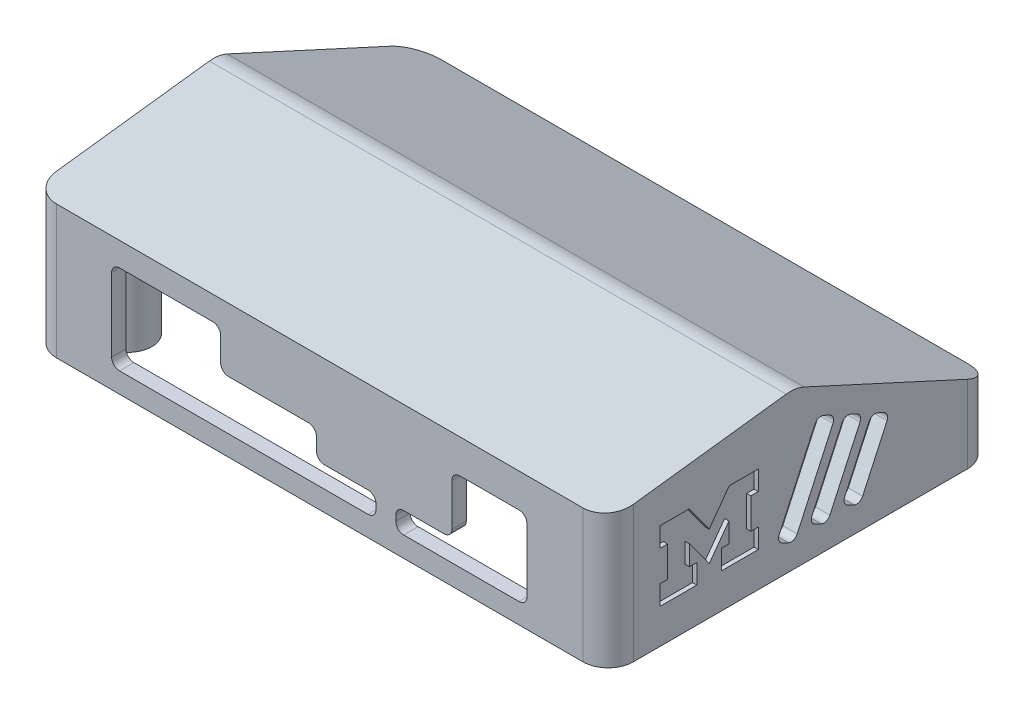
SolidWorks part; units mm, degrees
ref_plane "Front Plane" through (0, 0, 0) normal (0, 0, 1) x (1, 0, 0)
ref_plane "Top Plane" through (0, 0, 0) normal (0, 1, 0) x (1, 0, 0)
ref_plane "Right Plane" through (0, 0, 0) normal (1, 0, 0) x (0, 0, -1)
sketch "Sketch1" plane through (0, 0, 0) normal (0, 1, 0) x (1, 0, 0)
  line L0 (-37.7767, 21.1111) -> (-37.7767, -27.7389)
  line L1 (-34.6167, 23.6111) -> (43.3333, 23.6111)
  line L2 (-37.1167, 21.1111) -> (-37.1167, -27.7389)
  line L3 (-34.6167, -30.2389) -> (43.3333, -30.2389)
  line L4 (45.8333, 21.1111) -> (45.8333, -27.7389)
  line L5 (-34.6167, -30.8989) -> (43.3333, -30.8989)
  line L6 (46.4933, 21.1111) -> (46.4933, -27.7389)
  line L7 (-34.6167, 24.2711) -> (43.3333, 24.2711)
  arc A0 (-37.1167, -27.7389) -> (-34.6167, -30.2389) centre (-34.6167, -27.7389) ccw
  arc A1 (43.3333, -30.2389) -> (45.8333, -27.7389) centre (43.3333, -27.7389) ccw
  arc A2 (43.3333, 23.6111) -> (45.8333, 21.1111) centre (43.3333, 21.1111) cw
  arc A3 (-34.6167, 23.6111) -> (-37.1167, 21.1111) centre (-34.6167, 21.1111) ccw
  arc A4 (-37.7767, -27.7389) -> (-34.6167, -30.8989) centre (-34.6167, -27.7389) ccw
  arc A5 (43.3333, -30.8989) -> (46.4933, -27.7389) centre (43.3333, -27.7389) ccw
  arc A6 (43.3333, 24.2711) -> (46.4933, 21.1111) centre (43.3333, 21.1111) cw
  arc A7 (-34.6167, 24.2711) -> (-37.7767, 21.1111) centre (-34.6167, 21.1111) ccw
  point P8 (45.8333, -30.2389)
  point P11 (45.8333, 23.6111)
  point P14 (-37.1167, 23.6111)
  dimension "D3" = 2.5
  dimension "D1" = 82.95
  dimension "D2" = 53.85
  dimension "D4" = 0.66
extrude "Boss-Extrude1" add sketch "Sketch1" along normal blind 1.8
sketch "Sketch3" plane through (0, 1.8, 0) normal (0, 1, 0) x (1, 0, 0)
  line L8 (43.3333, 21.5611) -> (-34.6167, 21.5611)
  line L9 (-35.0667, 21.1111) -> (-35.0667, -27.7389)
  line L10 (-37.1167, 21.1111) -> (-37.1167, -27.7389)
  line L11 (-34.6167, -30.2389) -> (43.3333, -30.2389)
  line L33 (45.8333, -27.7389) -> (45.8333, 21.1111)
  line L34 (43.3333, 23.6111) -> (-34.6167, 23.6111)
  line L35 (-39.2917, 21.1111) -> (-39.2917, 25.7861)
  line L36 (-39.2917, 25.7861) -> (-34.6167, 25.7861)
  line L37 (43.3333, 25.7861) -> (-34.6167, 25.7861)
  line L38 (-39.2917, 21.1111) -> (-39.2917, -27.7389)
  line L39 (-34.6167, -32.4139) -> (43.3333, -32.4139)
  line L40 (48.0083, -27.7389) -> (48.0083, 21.1111)
  line L41 (43.3333, 25.7861) -> (-34.6167, 25.7861)
  line L42 (-39.2917, 21.1111) -> (-39.2917, -27.7389)
  line L43 (-34.6167, -32.4139) -> (43.3333, -32.4139)
  line L44 (48.0083, -27.7389) -> (48.0083, 21.1111)
  line L45 (-34.6167, 25.7861) -> (-34.5188, 25.7484)
  line L46 (48.0083, 21.1111) -> (48.0083, 25.7861)
  line L47 (48.0083, 25.7861) -> (43.3333, 25.7861)
  line L48 (43.3333, 25.7861) -> (43.4732, 25.7999)
  line L49 (48.0083, -27.7389) -> (48.0083, -32.4139)
  line L50 (48.0083, -32.4139) -> (43.3333, -32.4139)
  line L51 (-39.2917, -27.7389) -> (-39.2917, -32.4139)
  line L52 (-39.2917, -32.4139) -> (-34.6167, -32.4139)
  arc A6 (43.7833, 21.1111) -> (43.3333, 21.5611) centre (43.3333, 21.1111) ccw
  arc A7 (-34.6167, 21.5611) -> (-35.0667, 21.1111) centre (-34.6167, 21.1111) ccw
  arc A8 (43.7833, 21.1111) -> (43.3333, 21.5611) centre (43.3333, 21.1111) ccw
  arc A9 (-37.1167, -27.7389) -> (-34.6167, -30.2389) centre (-34.6167, -27.7389) ccw
  arc A21 (43.3333, -30.2389) -> (45.8333, -27.7389) centre (43.3333, -27.7389) ccw
  arc A22 (45.8333, 21.1111) -> (43.3333, 23.6111) centre (43.3333, 21.1111) ccw
  arc A23 (-34.6167, 23.6111) -> (-37.1167, 21.1111) centre (-34.6167, 21.1111) ccw
  arc A25 (43.3333, -32.4139) -> (48.0083, -27.7389) centre (43.3333, -27.7389) ccw
  arc A26 (48.0083, 21.1111) -> (43.3333, 25.7861) centre (43.3333, 21.1111) ccw
  arc A27 (-34.6167, 25.7861) -> (-39.2917, 21.1111) centre (-34.6167, 21.1111) ccw
  arc A28 (-39.2917, -27.7389) -> (-34.6167, -32.4139) centre (-34.6167, -27.7389) ccw
  arc A29 (43.3333, -32.4139) -> (48.0083, -27.7389) centre (43.3333, -27.7389) ccw
  arc A30 (48.0083, 21.1111) -> (43.3333, 25.7861) centre (43.3333, 21.1111) ccw
  arc A31 (-34.6167, 25.7861) -> (-39.2917, 21.1111) centre (-34.6167, 21.1111) ccw
  arc A32 (-39.2917, -27.7389) -> (-34.6167, -32.4139) centre (-34.6167, -27.7389) ccw
  arc M13 (-34.6167, 24.2711) -> (-37.7767, 21.1111) centre (-34.6167, 21.1111) ccw
  line M14 (-37.7767, 21.1111) -> (-37.7767, -27.7389)
  arc M15 (-37.7767, -27.7389) -> (-34.6167, -30.8989) centre (-34.6167, -27.7389) ccw
  line M16 (-34.6167, -30.8989) -> (43.3333, -30.8989)
  arc M17 (43.3333, -30.8989) -> (46.4933, -27.7389) centre (43.3333, -27.7389) ccw
  line M18 (46.4933, -27.7389) -> (46.4933, 21.1111)
  arc M19 (46.4933, 21.1111) -> (43.3333, 24.2711) centre (43.3333, 21.1111) ccw
  line M20 (43.3333, 24.2711) -> (-34.6167, 24.2711)
  line M21 (43.3333, -30.2389) -> (-34.6167, -30.2389)
  arc M22 (-34.6167, -30.2389) -> (-37.1167, -27.7389) centre (-34.6167, -27.7389) cw
  line M23 (-37.1167, -27.7389) -> (-37.1167, 21.1111)
  arc M24 (-37.1167, 21.1111) -> (-34.6167, 23.6111) centre (-34.6167, 21.1111) cw
  line M25 (-34.6167, 23.6111) -> (43.3333, 23.6111)
  arc M26 (43.3333, 23.6111) -> (45.8333, 21.1111) centre (43.3333, 21.1111) cw
  line M27 (45.8333, 21.1111) -> (45.8333, -27.7389)
  arc M28 (45.8333, -27.7389) -> (43.3333, -30.2389) centre (43.3333, -27.7389) cw
  dimension "D1" = 2.05
  dimension "D2" = 2.175
  dimension "D3" = 2.175
extrude "Boss-Extrude3" add sketch "Sketch3" along normal blind 10 contours L42 A32 L43 A29 L44 A30 L41 A31 M13 M20 M19 M18 M17 M16 M15 M14 | A32 L51 L52 | M20 M13 M14 M15 M16 M17 M18 M19 M28 M21 M22 M23 M24 M25 M26 M27 | A31 L36 L35 | A30 L46 L47 | A29 L50 L49 region at (-37.1805, 1.8, -23.6749) region at (-38.2474, 1.8, -24.7419) region at (-38.2474, 1.8, 31.3696) region at (46.9641, 1.8, -24.7419) region at (46.9641, 1.8, 31.3696) region at (4.3583, 1.8, -24.1704)
sketch "Sketch4" plane through (0, 0, -25.7861) normal (0, 0, -1) x (-1, 0, 0)
  line L0 (-4.3583, 1.8) -> (-4.3583, 25.0723)
  line L1 (-48.0083, 1.8) -> (39.2917, 1.8) construction
  line L2 (7.9607, 1.8) -> (7.9607, 25.0723)
  line L3 (20.6617, 1.8) -> (20.6617, 22.638)
  line L4 (7.9607, 5.44) -> (20.6617, 5.44)
  line L5 (4.5182, 1.8) -> (4.5182, -0.6587)
  line L6 (11.4031, 1.8) -> (11.4031, -0.6587)
  line L7 (11.4031, -0.6587) -> (4.5182, -0.6587)
  line L8 (17.2192, 1.8) -> (17.2192, -1.5181)
  line L9 (24.1041, -1.5181) -> (17.2192, -1.5181)
  line L10 (24.1041, 1.8) -> (24.1041, -1.5181)
  line L11 (-48.0083, 1.8) -> (39.2917, 1.8) construction
  circle A0 centre (7.9607, 5.44) radius 5.01
  circle A1 centre (20.6617, 5.44) radius 5.01
  line M1 (-48.0083, 1.8) -> (39.2917, 1.8)
  dimension "D4" = 10.02
  dimension "D5" = 10.02
  dimension "D2" = 25.02
  dimension "D3" = 3.64
  dimension "D1" = 12.319
extrude "Cut-Extrude1" cut sketch "Sketch4" against normal blind 5 contours L2 A0 M1 | A0 L4 L2 M1 | L4 A0 L2 | A0 L5 L7 L6 | A0 M1 | A1 L8 L9 L10 | A1 region at (-5.762, 5.8158, -25.7861) region at (-7.9607, 1.245, -25.7861) region at (-10.246, 3.7208, -25.7861) region at (-10.087, 7.5663, -25.7861) region at (-7.9607, 0.1521, -25.7861) region at (-20.6617, -0.2965, -25.7861)
sketch "Sketch5" plane through (0, 0, -25.7861) normal (0, 0, -1) x (-1, 0, 0)
  line L0 (-4.3583, 11.8) -> (-4.3583, -7.2365)
  line L1 (-48.0083, 11.8) -> (39.2917, 11.8) construction
  line L2 (-17.3383, 11.8) -> (-17.3383, -7.2365)
  line L3 (-48.0083, 1.8) -> (4.5182, 1.8) construction
  line L5 (-17.3383, 1.8) -> (-17.3383, 8.55)
  line L6 (-17.3383, 8.55) -> (-10.9347, 8.55)
  line L8 (-4.6583, 11.8) -> (-4.6583, -7.2365)
  line L9 (-4.6583, 8.55) -> (-7.6243, 8.55)
  circle A0 centre (-17.3383, 8.55) radius 1.69
  circle A1 centre (-17.3383, 8.55) radius 2.19
  circle A2 centre (-4.6583, 8.55) radius 1.69
  circle A3 centre (-4.6583, 8.55) radius 2.19
  dimension "D3" = 3.38
  dimension "D6" = 3.38
  dimension "D2" = 6.75
  dimension "D1" = 12.98
  dimension "D4" = 0.5
  dimension "D5" = 0.3
  dimension "D7" = 0.5
extrude "Cut-Extrude2" cut sketch "Sketch5" against normal blind 5 contours A3 | A1
sketch "Sketch6" plane through (0, 11.8, 0) normal (0, 1, 0) x (1, 0, 0)
  line L0 (-37.1167, -3.3139) -> (-39.2917, -3.3139)
  line L2 (-37.1167, -27.7389) -> (-37.1167, 21.1111) construction
  line L3 (-37.1167, -3.3139) -> (45.8333, -3.3139)
  line L4 (45.8333, 21.1111) -> (45.8333, -27.7389) construction
  line L5 (45.8333, -3.3139) -> (48.0083, -3.3139)
  line L19 (48.0083, -28.6139) -> (48.0083, -32.4139)
  line L20 (48.0083, -32.4139) -> (44.2083, -32.4139)
  line L21 (-39.2917, -28.6139) -> (-39.2917, -32.4139)
  line L22 (48.0083, -28.6139) -> (48.0083, 25.7861)
  line L23 (-35.4917, -32.4139) -> (44.2083, -32.4139)
  line L24 (-39.2917, 25.7861) -> (-39.2917, -28.6139)
  line L31 (-39.2917, -32.4139) -> (-35.4917, -32.4139)
  line L37 (45.8333, 21.1111) -> (45.8333, -27.7389)
  line L38 (43.3333, -30.2389) -> (-34.6167, -30.2389)
  line L39 (-37.1167, -27.7389) -> (-37.1167, 21.1111)
  arc A20 (43.3333, -30.2389) -> (45.8333, -27.7389) centre (43.3333, -27.7389) ccw
  arc A21 (-37.1167, -27.7389) -> (-34.6167, -30.2389) centre (-34.6167, -27.7389) ccw
  line M11 (-39.2917, 25.7861) -> (-39.2917, -32.4139)
  line M13 (-39.2917, -32.4139) -> (48.0083, -32.4139)
  line M15 (48.0083, -32.4139) -> (48.0083, 25.7861)
  arc M19 (45.8333, -27.7389) -> (43.3333, -30.2389) centre (43.3333, -27.7389) cw
  line M20 (43.3333, -30.2389) -> (-34.6167, -30.2389)
  arc M21 (-34.6167, -30.2389) -> (-37.1167, -27.7389) centre (-34.6167, -27.7389) cw
  line M22 (-37.1167, -27.7389) -> (-37.1167, 21.1111)
  line M26 (45.8333, 21.1111) -> (45.8333, -27.7389)
  dimension "D3" = 29.1
extrude "Boss-Extrude4" add sketch "Sketch6" along normal blind 8 contours M26 M19 M20 M21 M22 M11 M13 M15 region at (-38.0369, 11.8, 15.5264)
sketch "Sketch7" plane through (0, 19.8, 0) normal (0, 1, 0) x (1, 0, 0)
  line L0 (-39.2917, -30.2389) -> (48.0083, -30.2389)
  line L1 (48.0083, -31.3688) -> (48.0083, -32.4139)
  line L2 (48.0083, -32.4139) -> (44.2083, -32.4139)
  line L3 (-39.2917, -31.3688) -> (-39.2917, -32.4139)
  line L4 (-39.2917, -32.4139) -> (-35.4917, -32.4139)
  line L8 (43.3333, -30.2389) -> (-34.6167, -30.2389) construction
  line L9 (-39.2917, -3.3139) -> (-39.2917, -32.4139) construction
  line L10 (48.0083, -32.4139) -> (48.0083, -3.3139) construction
  line L19 (-35.4917, -32.4139) -> (44.2083, -32.4139)
  line L20 (-39.2917, -30.2389) -> (-39.2917, -31.3688)
  line L21 (48.0083, -31.3688) -> (48.0083, -30.2389)
  dimension "D1" = 2.175
  dimension "D2" = 2.175
extrude "Boss-Extrude5" add sketch "Sketch7" along normal blind 2.175
sketch "Sketch15" plane through (0, 0, 32.4139) normal (0, 0, 1) x (1, 0, 0)
  line L0 (4.3583, 4.8675) -> (4.3583, 8.0675)
  line L1 (-39.2917, 1.8) -> (48.0083, 1.8) construction
  line L2 (-39.2917, 21.975) -> (48.0083, 21.975) construction
  line L3 (-27.1327, 4.8675) -> (12.8673, 4.8675)
  line L4 (-27.1327, 4.8675) -> (12.8673, 4.8675)
  line L6 (-18.8827, 4.8675) -> (-18.8827, 18.3675)
  line L7 (-10.6327, 4.8675) -> (-10.6327, 18.3675)
  line L8 (-27.1327, 4.8675) -> (-27.1327, 18.3675)
  line L9 (-27.1327, 18.3675) -> (-10.6327, 18.3675)
  line L10 (4.3583, 18.3675) -> (48.0083, 18.3675)
  line L11 (-39.2917, 18.3675) -> (48.0083, 18.3675) construction
  line L12 (-27.1327, 1.8) -> (-27.1327, 21.975) construction
  line L13 (-10.6327, 1.8) -> (-10.6327, 21.975) construction
  line L14 (3.8673, 4.8675) -> (3.8673, 12.3675)
  line L15 (-10.6327, 12.3675) -> (3.8673, 12.3675)
  line L16 (12.8673, 4.8675) -> (12.8673, 8.0675)
  line L17 (3.8673, 4.8675) -> (3.8673, 18.3675) construction
  line L18 (3.8673, 8.0675) -> (12.8673, 8.0675)
  line L19 (15.8673, 4.8675) -> (15.8673, 8.0675)
  line L20 (12.8673, 4.8675) -> (12.8673, 12.3675) construction
  line L22 (15.8673, 8.0675) -> (24.3673, 8.0675)
  line L23 (30.4695, 4.8675) -> (30.4695, 16.8675)
  line L24 (35.7195, 4.8675) -> (35.7195, 16.8675)
  line L26 (25.2195, 16.8675) -> (35.7195, 16.8675)
  line L27 (25.2195, 18.3675) -> (25.2195, 21.975)
  line L28 (35.7195, 18.3675) -> (35.7195, 21.975)
  line L30 (4.3583, 18.3675) -> (4.3583, 21.975)
  line L31 (35.7195, 1.8) -> (35.7195, 21.975) construction
  line L32 (-18.8827, 1.8) -> (-18.8827, 21.975) construction
  line L33 (-39.2917, 4.8675) -> (48.0083, 4.8675) construction
  line L34 (25.2195, 4.8675) -> (35.7195, 4.8675)
  line L35 (4.3583, 1.8) -> (4.3583, 21.975) construction
  line L36 (30.4695, 1.8) -> (30.4695, 21.975) construction
  line L37 (15.8673, 4.8675) -> (24.3673, 4.8675)
  line L38 (30.4695, 18.3675) -> (30.4695, 21.975)
  line L39 (-27.1327, 4.8675) -> (-27.1327, 18.3675)
  line L40 (-10.6327, 18.3675) -> (-10.6327, 12.3675)
  line L41 (3.8673, 12.3675) -> (3.8673, 8.0675)
  line L42 (15.8673, 4.8675) -> (24.3673, 4.8675)
  line L44 (35.7195, 16.8675) -> (35.7195, 4.8675)
  line L45 (25.2195, 4.8675) -> (35.7195, 4.8675)
  line L46 (25.2195, 16.8675) -> (24.3673, 16.8675)
  line L47 (24.3673, 16.8675) -> (24.3673, 8.0675)
  line L48 (24.3673, 4.8675) -> (25.2195, 4.8675)
  point P41 (25.2195, 1.8)
  dimension "D1" = 3.0675
  dimension "D7" = 7.5
  dimension "D9" = 3.2
  dimension "D15" = 12
  dimension "D2" = 23.241
  dimension "D3" = 8.25
  dimension "D4" = 8.25
  dimension "D5" = 13.5
  dimension "D6" = 14.5
  dimension "D8" = 9
  dimension "D10" = 3
  dimension "D12" = 26.1112
  dimension "D13" = 5.25
extrude "Cut-Extrude3" cut sketch "Sketch15" against normal blind 2.175 contours L9 L8 L3 L6 | L9 L6 L4 L7 | L15 L7 L3 L14 | L18 L0 L3 L16 | L18 L14 L4 L0 | L19 L37 L22 | L34 L23 L26 | L23 L34 L24 L26 region at (4.1128, 6.4675, 32.4139) region at (8.6128, 6.4675, 32.4139) region at (-3.3827, 8.6175, 32.4139) region at (-14.7577, 11.6175, 32.4139) region at (-23.0077, 11.6175, 32.4139) region at (25.441, 9.6758, 32.4139) region at (33.0945, 10.8675, 32.4139)
sketch "Sketch24" plane through (-39.2917, 0, 0) normal (-1, 0, 0) x (0, 0, 1)
  line L0 (32.146, 19.8166) -> (4.3973, 23.2604)
  line L1 (4.3973, 23.2604) -> (-20.572, 11.8)
  line L2 (32.146, 19.8166) -> (32.4139, 19.8166)
  line L3 (32.4139, 21.975) -> (32.4139, 1.8) construction
  line L4 (32.4139, 19.8166) -> (32.4139, 21.975)
  line L5 (-25.7861, 11.8) -> (-20.572, 11.8)
  line L10 (4.3973, 23.2604) -> (-24.8788, 9.8233) construction
  line L23 (32.4139, 21.975) -> (4.0518, 25.495)
  line L24 (4.0518, 25.495) -> (-25.7861, 11.8)
  dimension "D1" = 2.175
extrude "Boss-Extrude11" add sketch "Sketch24" against normal up to surface (87.3 mm away) up to face at (48.0083, 14.4797, 13.5467)
sketch "Sketch28" plane through (-39.2917, 0, 0) normal (-1, 0, 0) x (0, 0, 1)
  line L0 (-20.572, 11.8) -> (4.3973, 23.2604)
  line L1 (4.3973, 23.2604) -> (30.2389, 20.0533)
  line L2 (30.2389, 20.0533) -> (30.2389, 19.8)
  line L3 (30.2389, 19.8) -> (3.3139, 19.8)
  line L4 (3.3139, 19.8) -> (3.3139, 11.8)
  line L5 (3.3139, 11.8) -> (-20.572, 11.8)
extrude "Boss-Extrude12" add sketch "Sketch28" against normal blind 2.175
sketch "Sketch29" plane through (48.0083, 0, 0) normal (1, 0, 0) x (0, 0, -1)
  line L0 (-30.2389, 20.0533) -> (-30.2389, 19.8)
  line L1 (-30.2389, 19.8) -> (-3.3139, 19.8)
  line L2 (-3.3139, 19.8) -> (-3.3139, 11.8)
  line L3 (-3.3139, 11.8) -> (20.572, 11.8)
  line L4 (20.572, 11.8) -> (-4.3973, 23.2604)
  line L5 (-4.3973, 23.2604) -> (-30.2389, 20.0533)
extrude "Boss-Extrude13" add sketch "Sketch29" against normal blind 2.175
sketch "Sketch32" plane through (48.0083, 0, 0) normal (1, 0, 0) x (0, 0, -1)
  line L0 (0.7555, 23.2886) -> (-6.9465, 6.5079)
  line L1 (25.7861, 11.8) -> (-4.0518, 25.495) construction
  line L2 (-6.9465, 6.5079) -> (-4.22, 5.2564)
  line L3 (-4.22, 5.2564) -> (2.0259, 18.8647)
  line L4 (2.0259, 18.8647) -> (-0.7006, 20.1161)
  line L5 (-2.8567, 4.6307) -> (-2.5695, 5.2564)
  line L7 (-1.9952, 6.5079) -> (3.3892, 18.239)
  line L8 (0.7314, 5.2564) -> (6.1157, 16.9876)
  line L9 (0.7314, 5.2564) -> (-1.9952, 6.5079)
  line L10 (-0.1302, 3.3793) -> (6.1157, 16.9876) construction
  line L12 (-2.8567, 4.6307) -> (3.3892, 18.239) construction
  line L14 (5.6827, 5.2564) -> (10.2055, 15.1104)
  line L16 (6.1157, 16.9876) -> (3.3892, 18.239)
  line L17 (7.479, 16.3618) -> (10.2055, 15.1104)
  line L18 (5.6827, 5.2564) -> (2.9562, 6.5079)
  line L19 (2.9562, 6.5079) -> (7.479, 16.3618)
  point P11 (2.0946, 4.6307)
  point P16 (3.4579, 4.005)
  point P17 (8.8422, 15.7361)
  point P18 (4.8211, 3.3793)
  dimension "D1" = 3
  dimension "D2" = 1.5
  dimension "D3" = 3
extrude "Cut-Extrude6" cut sketch "Sketch32" against normal through all contours L3 L4 L0 L2 | L8 L16 L7 L9 | L19 L18 L14 L17 region at (48.0083, 12.6863, 2.4603) region at (48.0083, 11.7477, -2.0603) region at (48.0083, 10.8091, -6.5808)
fillet "Fillet7" radius 1 24 edges at (46.9208, 5.2564, 4.22) (46.9208, 5.2564, -0.7314) (46.9208, 5.2564, -5.6827) (46.9208, 18.8647, -2.0259) (46.9208, 16.9876, -6.1157) (46.9208, 15.1104, -10.2055) (46.9208, 6.5079, 6.9465) (46.9208, 6.5079, 1.9952) (46.9208, 6.5079, -2.9562) (46.9208, 16.3618, -7.479) (46.9208, 20.1161, 0.7006) (46.9208, 18.239, -3.3892) (-38.2042, 16.9876, -6.1157) (-38.2042, 18.8647, -2.0259) (-38.2042, 15.1104, -10.2055) (-38.2042, 5.2564, -5.6827) (-38.2042, 5.2564, -0.7314) (-38.2042, 6.5079, -2.9562) (-38.2042, 6.5079, 1.9952) (-38.2042, 6.5079, 6.9465) (-38.2042, 16.3618, -7.479) (-38.2042, 18.239, -3.3892) (-38.2042, 20.1161, 0.7006) (-38.2042, 5.2564, 4.22)
fillet "Fillet1" radius 3.8 2 edges at (-39.2917, 11.8875, 32.4139) (48.0083, 11.8875, 32.4139)
fillet "Fillet2" radius 3.8 2 edges at (-39.2917, 6.8, -25.7861) (48.0083, 6.8, -25.7861)
fillet "Fillet4" radius 1.2 14 edges at (15.8673, 4.8675, 31.3264) (35.7195, 4.8675, 31.3264) (12.8673, 4.8675, 31.3264) (15.8673, 8.0675, 31.3264) (35.7195, 16.8675, 31.3264) (3.8673, 8.0675, 31.3264) (12.8673, 8.0675, 31.3264) (3.8673, 12.3675, 31.3264) (-10.6327, 18.3675, 31.3264) (-10.6327, 12.3675, 31.3264) (-27.1327, 18.3675, 31.3264) (-27.1327, 4.8675, 31.3264) (24.3673, 16.8675, 31.3264) (24.3673, 8.0675, 31.3264)
fillet "Fillet6" [suppressed] radius 1.5
sketch "Sketch20" plane through (0, 0, 0) normal (0, -1, 0) x (1, 0, 0)
  line L2 (-31.9917, -18.4361) -> (-37.1167, -18.4361) construction
  line L3 (-37.1167, -21.1111) -> (-37.1167, 27.7389) construction
  line L4 (40.7083, -18.4361) -> (45.8333, -18.4361) construction
  line L5 (45.8333, 27.7389) -> (45.8333, -21.1111) construction
  line L6 (-31.9917, 25.0639) -> (-31.9917, 30.2389) construction
  line L7 (-34.6167, 30.2389) -> (43.3333, 30.2389) construction
  line L8 (-31.9917, -18.4361) -> (-31.9917, -23.6111) construction
  line L9 (-24.1041, -23.6111) -> (-34.6167, -23.6111) construction
  circle A0 centre (-31.9917, -18.4361) radius 3.6
  circle A1 centre (-31.9917, -18.4361) radius 2.125
  circle A2 centre (40.7083, -18.4361) radius 2.125
  circle A3 centre (40.7083, -18.4361) radius 3.6
  circle A4 centre (40.7083, 25.0639) radius 2.125
  circle A5 centre (40.7083, 25.0639) radius 3.6
  circle A6 centre (-31.9917, 25.0639) radius 2.125
  circle A7 centre (-31.9917, 25.0639) radius 3.6
  dimension "D1" = 7.2
  dimension "D2" = 4.25
  dimension "D7" = 4.25
  dimension "D8" = 4.25
  dimension "D9" = 4.25
  dimension "D5" = 72.7
  dimension "D6" = 43.5
  dimension "D3" = 2
  dimension "D4" = 2
extrude "Boss-Extrude9" add sketch "Sketch20" against normal up to surface (18.0123 mm away) from offset 3.13 contours A5 A4 | A7 A6 region at (37.2102, 0, 25.0639) region at (-35.4898, 0, 25.0639) up to face at (4.3583, 21.6568, 17.3181) offset against normal yes
sketch "Sketch22" plane through (-39.2917, 0, 0) normal (-1, 0, 0) x (0, 0, 1)
  line L0 (28.6139, 1.8) -> (37.2656, 1.8)
  line L1 (37.2656, 1.8) -> (37.2656, 0)
  line L2 (37.2656, 0) -> (-27.0337, 0)
  line L3 (-27.0337, 0) -> (-27.0337, 1.8)
  line L4 (-27.0337, 1.8) -> (28.6139, 1.8)
extrude "Cut-Extrude4" cut sketch "Sketch22" against normal through all
sketch "Sketch23" plane through (-39.2917, 0, 0) normal (-1, 0, 0) x (0, 0, 1)
  line L0 (3.3139, 1.8) -> (3.3139, 3.3)
  line L1 (-21.9861, 1.8) -> (28.6139, 1.8) construction
  line L2 (3.3139, 3.3) -> (-5.2861, 3.3)
  line L3 (-5.2861, 3.3) -> (-5.2861, 1.8)
  line L4 (-5.2861, 1.8) -> (7.2139, 1.8)
  line L5 (7.2139, 1.8) -> (7.2139, 3.3)
  line L6 (7.2139, 3.3) -> (3.3139, 3.3)
  line M4 (-21.9861, 1.8) -> (28.6139, 1.8)
  dimension "D1" = 1.5
  dimension "D2" = 8.6
  dimension "D3" = 12.5
extrude "Cut-Extrude5" cut sketch "Sketch23" against normal blind 2.175 contours L2 L3 L0 M4 | L5 L6 L0 M4 region at (-39.2917, 2.55, -0.9861) region at (-39.2917, 2.55, 5.2639)
extrude "Boss-Extrude14" add sketch "Sketch20<4>" against normal up to next from offset 3.13 contours A3 A2 | A0 A1 region at (-35.4898, 0, -18.4361) region at (37.2102, 0, -18.4361) offset against normal yes
sketch "Sketch20<4>" plane through (0, 0, 0) normal (0, -1, 0) x (1, 0, 0) same geometry as "Sketch20"
fillet "Fillet8" radius 5 1 edges at (4.3583, 25.495, 4.0518)
sketch "Sketch33" plane through (48.0083, 0, 0) normal (1, 0, 0) x (0, 0, -1)
  line L0 (-24.5468, 17.6178) -> (-24.5468, 14.6578)
  line L1 (-24.5468, 14.6578) -> (-23.4268, 14.6578)
  line L2 (-23.4268, 14.6578) -> (-23.4268, 10.0178)
  line L3 (-23.4268, 10.0178) -> (-24.5468, 10.0178)
  line L4 (-24.5468, 10.0178) -> (-24.5468, 7.0578)
  line L5 (-24.5468, 7.0578) -> (-18.9948, 7.0578)
  line L6 (-18.9948, 7.0578) -> (-18.9948, 10.0178)
  line L7 (-18.9948, 10.0178) -> (-20.1148, 10.0178)
  line L8 (-20.1148, 10.0178) -> (-20.1148, 13.0258)
  line L9 (-20.1148, 13.0258) -> (-17.1228, 8.9315)
  line L11 (-17.1228, 13.4578) -> (-14.0828, 17.6178)
  line L12 (-14.1308, 13.0258) -> (-17.1228, 8.9315)
  line L13 (-14.0828, 17.6178) -> (-9.6988, 17.6178)
  line L14 (-14.1308, 10.0178) -> (-14.1308, 13.0258)
  line L15 (-15.2508, 10.0178) -> (-14.1308, 10.0178)
  line L16 (-15.2508, 7.0578) -> (-15.2508, 10.0178)
  line L17 (-9.6988, 7.0578) -> (-15.2508, 7.0578)
  line L18 (-9.6988, 10.0178) -> (-9.6988, 7.0578)
  line L19 (-10.8188, 10.0178) -> (-9.6988, 10.0178)
  line L20 (-10.8188, 14.6578) -> (-10.8188, 10.0178)
  line L21 (-9.6988, 14.6578) -> (-10.8188, 14.6578)
  line L22 (-17.1228, 13.4578) -> (-20.1628, 17.6178)
  line L23 (-20.1628, 17.6178) -> (-24.5468, 17.6178)
  line L24 (-9.6988, 17.6178) -> (-9.6988, 14.6578)
extrude "Cut-Extrude7" cut sketch "Sketch33" against normal blind 0.65
sketch "Sketch34" plane through (0, 3.13, 0) normal (0, -1, 0) x (1, 0, 0)
  line L0 (-34.0584, 27.1602) -> (-35.4917, 28.6139)
  line L1 (-35.4917, 28.6139) -> (-37.0054, 30.1493)
  line L2 (-33.3463, 27.8622) -> (-34.7796, 29.316)
  line L3 (-34.7796, 29.316) -> (-36.2933, 30.8514)
  line L4 (-34.7705, 26.4581) -> (-36.2038, 27.9118)
  line L5 (-36.2038, 27.9118) -> (-37.7175, 29.4472)
  line L6 (-37.7175, 29.4472) -> (-36.2933, 30.8514)
  line L7 (-33.3463, 27.8622) -> (-34.7705, 26.4581)
  line L8 (4.3583, 4.3973) -> (4.3583, 42.8593)
  line L9 (-36.2038, 27.9118) -> (-41.7788, 33.5665) construction
  line L10 (-35.4917, 28.6139) -> (-41.0667, 34.2685) construction
  line L11 (-34.7796, 29.316) -> (-40.3546, 34.9706) construction
  line L12 (-31.2796, 25.766) -> (-34.7796, 29.316) construction
  line L13 (-31.9917, 25.0639) -> (-35.4917, 28.6139) construction
  line L14 (-32.7038, 24.3618) -> (-36.2038, 27.9118) construction
  line L15 (45.8333, 4.3973) -> (-37.1167, 4.3973) construction
  line L16 (42.063, 27.8622) -> (43.4872, 26.4581)
  line L17 (46.4342, 29.4472) -> (45.01, 30.8514)
  line L18 (44.9204, 27.9118) -> (46.4342, 29.4472)
  line L19 (43.4872, 26.4581) -> (44.9204, 27.9118)
  line L20 (43.4962, 29.316) -> (45.01, 30.8514)
  line L21 (42.063, 27.8622) -> (43.4962, 29.316)
  line L22 (44.2083, 28.6139) -> (45.7221, 30.1493)
  line L23 (42.7751, 27.1602) -> (44.2083, 28.6139)
  line L24 (4.3583, 4.3973) -> (27.2788, 4.3973)
  dimension "D1" = 1
  dimension "D2" = 1
extrude "Boss-Extrude16" add sketch "Sketch34" against normal up to surface (17.0215 mm away) contours L23 L19 L18 L17 L22 | L23 L22 L17 L20 L21 | L16 L23 L21 | L23 L16 L19 | L4 L5 L6 L3 L2 L7 region at (43.8925, 3.13, 29.0058) region at (44.6047, 3.13, 28.3037) up to face at (-31.9917, 20.2487, 28.6639)
sketch "Sketch35" plane through (0, 3.13, 0) normal (0, -1, 0) x (1, 0, 0)
  line L0 (-33.9029, -20.3838) -> (-34.6167, -21.1111)
  line L1 (4.3583, 4.3973) -> (4.3583, -49.3158)
  line L2 (-34.6167, -19.6834) -> (-35.3304, -20.4107)
  line L3 (-35.3304, -20.4107) -> (-37.7084, -22.8339)
  line L4 (-33.1892, -21.0842) -> (-33.9029, -21.8115)
  line L5 (-33.9029, -21.8115) -> (-36.2809, -24.2347)
  line L6 (-37.7084, -22.8339) -> (-36.2809, -24.2347)
  line L7 (-34.6167, -19.6834) -> (-33.1892, -21.0842)
  line L8 (45.8333, 4.3973) -> (-37.1167, 4.3973) construction
  line L9 (-32.7054, -17.7357) -> (-35.3304, -20.4107) construction
  line L10 (-31.9917, -18.4361) -> (-34.6167, -21.1111) construction
  line L11 (-31.2779, -19.1365) -> (-33.9029, -21.8115) construction
  line L12 (-33.9029, -21.8115) -> (-39.6975, -27.7164) construction
  line L13 (-34.6167, -21.1111) -> (-40.4112, -27.016) construction
  line L14 (-35.3304, -20.4107) -> (-41.125, -26.3156) construction
  line L15 (43.3333, -19.6834) -> (41.9058, -21.0842)
  line L16 (46.425, -22.8339) -> (44.9975, -24.2347)
  line L17 (42.6196, -21.8115) -> (44.9975, -24.2347)
  line L18 (41.9058, -21.0842) -> (42.6196, -21.8115)
  line L19 (44.0471, -20.4107) -> (46.425, -22.8339)
  line L20 (43.3333, -19.6834) -> (44.0471, -20.4107)
  line L21 (42.6196, -20.3838) -> (43.3333, -21.1111)
  circle M4 centre (-31.9917, -18.4361) radius 3.6
  dimension "D1" = 1
  dimension "D2" = 1
extrude "Boss-Extrude17" add sketch "Sketch35" against normal up to next contours L3 L6 L5 L4 L2 M4 | L20 L15 L18 L17 L16 L19 region at (-35.7373, 3.13, -22.2531) region at (44.1654, 3.13, -21.9591)
